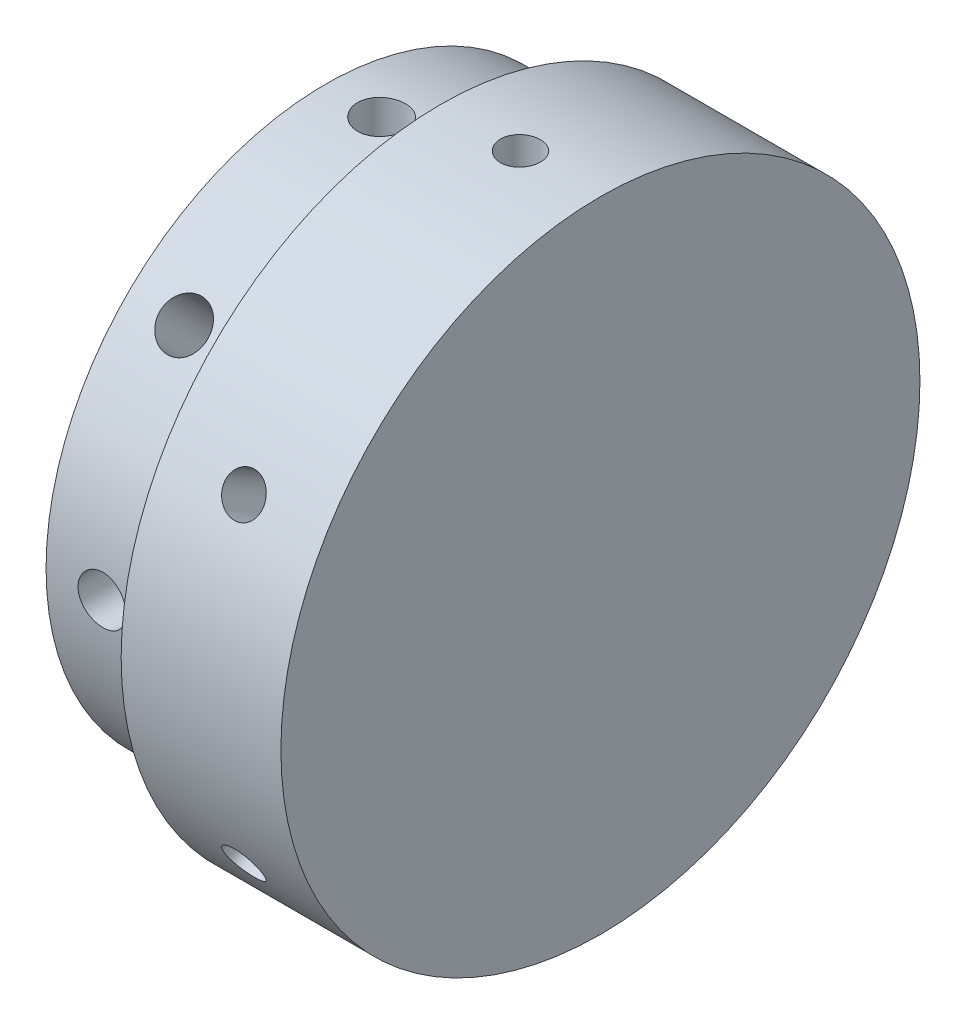
SolidWorks part; units mm, degrees
ref_plane "Front Plane" through (0, 0, 0) normal (0, 0, 1) x (1, 0, 0)
ref_plane "Top Plane" through (0, 0, 0) normal (0, 1, 0) x (1, 0, 0)
ref_plane "Right Plane" through (0, 0, 0) normal (1, 0, 0) x (0, 0, -1)
sketch "Sketch1" plane through (0, 0, 0) normal (1, 0, 0) x (0, 0, -1)
  circle A0 centre (0, 0) radius 30
  circle A1 centre (0, 0) radius 40
  dimension "D1" = 60
  dimension "D2" = 80
extrude "Boss-Extrude2" add sketch "Sketch1" along normal mid plane 20 contours A1
sketch "Sketch3" plane through (-10, 0, 0) normal (-1, 0, 0) x (0, 0, 1)
  circle A0 centre (0, 0) radius 35
  dimension "D1" = 70
ref_plane "Top Bolts" through (0, 40, 0) normal (0, 1, 0) x (1, 0, 0)
sketch "Sketch4" plane through (0, 40, 0) normal (0, 1, 0) x (1, 0, 0)
  line L0 (0, 0) -> (-10, 0) construction
  line L1 (-10, 40) -> (-10, -40) construction
  circle A0 centre (0, 0) radius 2.5
  point P5 (0, 0)
  dimension "D1" = 5
  dimension "D2" = 10
extrude "Cut-Extrude3" cut sketch "Sketch4" against normal blind 15.4
pattern_circular "CirPattern1" count 6 over 360 about axis through (-10, 0, 0) along (1, 0, 0) of "Cut-Extrude3"
extrude "Boss-Extrude4" add sketch "Sketch3" along normal blind 14.4 contours A0
ref_plane "Plane1" through (0, 35, 0) normal (0, 1, 0) x (1, 0, 0)
sketch "Sketch8" plane through (0, 35, 0) normal (0, 1, 0) x (1, 0, 0)
  line L0 (-24.4, 0) -> (-17.4, 0) construction
  line L1 (-24.4, 35) -> (-24.4, -35) construction
  circle A0 centre (-17.4, 0) radius 3
  dimension "D1" = 7
extrude "Cut-Extrude4" cut sketch "Sketch8" against normal blind 10
pattern_circular "CirPattern2" count 8 over 360 about axis through (-24.4, 0, 0) along (-1, 0, 0) of "Cut-Extrude4"
